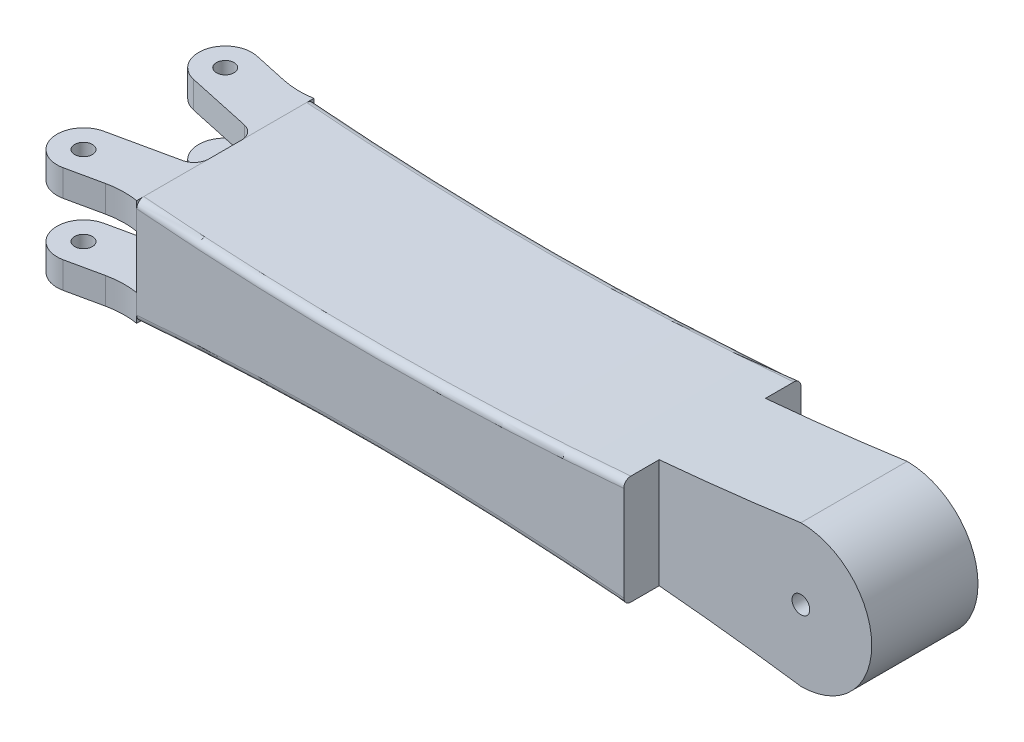
SolidWorks part; units mm, degrees
ref_plane "Front Plane" through (0, 0, 0) normal (0, 0, 1) x (1, 0, 0)
ref_plane "Top Plane" through (0, 0, 0) normal (0, 1, 0) x (1, 0, 0)
ref_plane "Right Plane" through (0, 0, 0) normal (1, 0, 0) x (0, 0, -1)
sketch "Sketch1" plane through (0, 0, 0) normal (0, 1, 0) x (1, 0, 0)
  line L1 (-125, -25) -> (125, -25)
  line L2 (-125, -25) -> (-125, 25)
  line L3 (-125, 25) -> (125, 25)
  line L4 (125, -25) -> (125, 25)
  line L5 (-125, -25) -> (125, 25) construction
  line L6 (-125, 25) -> (125, -25) construction
  point P0 (0, 0)
  dimension "D1" = 250
  dimension "D2" = 50
extrude "Boss-Extrude1" add sketch "Sketch1" along normal blind 55
sketch "Sketch4" plane through (0, 0, 25) normal (0, 0, 1) x (1, 0, 0)
  line L1 (-125, 55) -> (125, 55) construction
  line L2 (0, 0) -> (0, 55) construction
  line L3 (-72.5, 27.5) -> (105, 27.5) construction
  line L4 (125, 55) -> (125, 0) construction
  line L6 (-72.5, 42.5) -> (-72.5, 12.5)
  arc A1 (105, 47.5) -> (105, 7.5) centre (105, 27.5) cw
  arc A2 (105, 47.5) -> (-72.5, 42.5) centre (-6.1371, 839.7427) cw
  arc A3 (105, 7.5) -> (-72.5, 12.5) centre (-6.1371, -784.7427) ccw
  point P1 (0, 0)
  point P2 (0, 27.5)
  point P3 (0, 0)
  dimension "D1" = 15
  dimension "D2" = 0
  dimension "D3" = 20
  dimension "D4" = 800
extrude "Cut-Extrude2" cut sketch "Sketch4" against normal through all both and the other way through all flip side to cut
fillet "Fillet2" radius 2 4 edges at (16.3892, 40.0599, -25) (16.3892, 14.9401, -25) (16.3892, 40.0599, 25) (16.3892, 14.9401, 25)
sketch "Sketch7" plane through (0, 0, 25) normal (0, 0, 1) x (1, 0, 0)
  line L0 (0, 0) -> (0, 71.1105) construction
  circle A1 centre (105, 27.5) radius 2.5
  dimension "D1" = 5
extrude "Cut-Extrude3" cut sketch "Sketch7" against normal through all both and the other way through all
sketch "Sketch12" plane through (0, 0, 25) normal (0, 0, 1) x (1, 0, 0)
  line L1 (65, 59.9914) -> (151.4692, 59.9914)
  line L2 (65, 59.9914) -> (65, -4.7188)
  line L3 (65, -4.7188) -> (151.4692, -4.7188)
  line L4 (151.4692, 59.9914) -> (151.4692, -4.7188)
  arc A0 (111.4942, 8.5837) -> (111.4942, 46.4163) centre (105, 27.5) ccw construction
  point P7 (125, 27.5)
  point P8 (151.4692, -4.7188)
  dimension "D1" = 60
extrude "Cut-Extrude7" cut sketch "Sketch12" against normal blind 10
sketch "Sketch13" plane through (0, 0, -25) normal (0, 0, -1) x (-1, 0, 0)
  line L0 (-65, 42.9118) -> (-65, 12.0882) construction
  line L1 (-65, 42.9118) -> (-65, 12.0882)
  arc A0 (-65, 12.0882) -> (-105, 7.5) centre (6.1371, -784.7427) ccw construction
  arc A1 (-105, 47.5) -> (-65, 42.9118) centre (6.1371, 839.7427) ccw construction
  arc A2 (-105, 47.5) -> (-105, 7.5) centre (-105, 27.5) ccw construction
  arc A3 (-65, 12.0882) -> (-105, 7.5) centre (6.1371, -784.7427) ccw
  arc A4 (-105, 47.5) -> (-65, 42.9118) centre (6.1371, 839.7427) ccw
  arc A5 (-105, 47.5) -> (-105, 7.5) centre (-105, 27.5) ccw
extrude "Cut-Extrude8" cut sketch "Sketch13" against normal blind 10
ref_plane "Plane1" through (0, 42.5, 0) normal (0, -1, 0) x (0, 0, 1)
sketch "Sketch14" plane through (0, 42.5, 0) normal (0, -1, 0) x (0, 0, 1)
  line L0 (-8.0024, 72.5) -> (-12.6694, 94.085)
  line L1 (-27.3306, 90.915) -> (-23.349, 72.5)
  line L2 (-23, 72.5) -> (23, 72.5) construction
  line L3 (-20, 92.5) -> (0, 0) construction
  line L4 (0, 0) -> (-23, 0) construction
  line L5 (-23, -65) -> (-23, 72.5) construction
  line L6 (0, 0) -> (0, 72.5) construction
  line L7 (27.3306, 90.915) -> (23.349, 72.5)
  line L8 (8.0024, 72.5) -> (12.6694, 94.085)
  line L9 (8.0024, 72.5) -> (23.349, 72.5)
  line L10 (-8.0024, 72.5) -> (-23.349, 72.5)
  arc A1 (-12.6694, 94.085) -> (-27.3306, 90.915) centre (-20, 92.5) ccw
  arc A2 (12.6694, 94.085) -> (27.3306, 90.915) centre (20, 92.5) cw
  circle A3 centre (-20, 92.5) radius 2.5
  circle A4 centre (20, 92.5) radius 2.5
  dimension "D1" = 7.5
  dimension "D2" = 5
  dimension "D3" = 20
  dimension "D4" = 20
  dimension "D5" = 0
  dimension "D6" = 180
extrude "Boss-Extrude2" add sketch "Sketch14" along normal up to vertex (30 mm away)
sketch "Sketch16" plane through (-72.5, 0, 0) normal (-1, 0, 0) x (0, 0, 1)
  line L0 (-27.5, 12.5) -> (-12.6694, 12.5) construction
  line L1 (-43.7481, 35) -> (52.5143, 35)
  line L2 (-43.7481, 35) -> (-43.7481, 20)
  line L3 (-43.7481, 20) -> (52.5143, 20)
  line L4 (52.5143, 35) -> (52.5143, 20)
  point P4 (-43.7481, 27.5)
  dimension "D1" = 15
  dimension "D2" = 15
extrude "Cut-Extrude9" cut sketch "Sketch16" along normal blind 50
fillet "Fillet3" radius 4.2 4 edges at (-72.5, 16.25, 8.0024) (-72.5, 16.25, -8.0024) (-72.5, 38.75, 8.0024) (-72.5, 38.75, -8.0024)
fillet "Fillet4" radius 23 4 edges at (-72.5, 16.2654, -23.349) (-72.5, 38.7346, -23.349) (-72.5, 16.2654, 23.349) (-72.5, 38.7346, 23.349)
